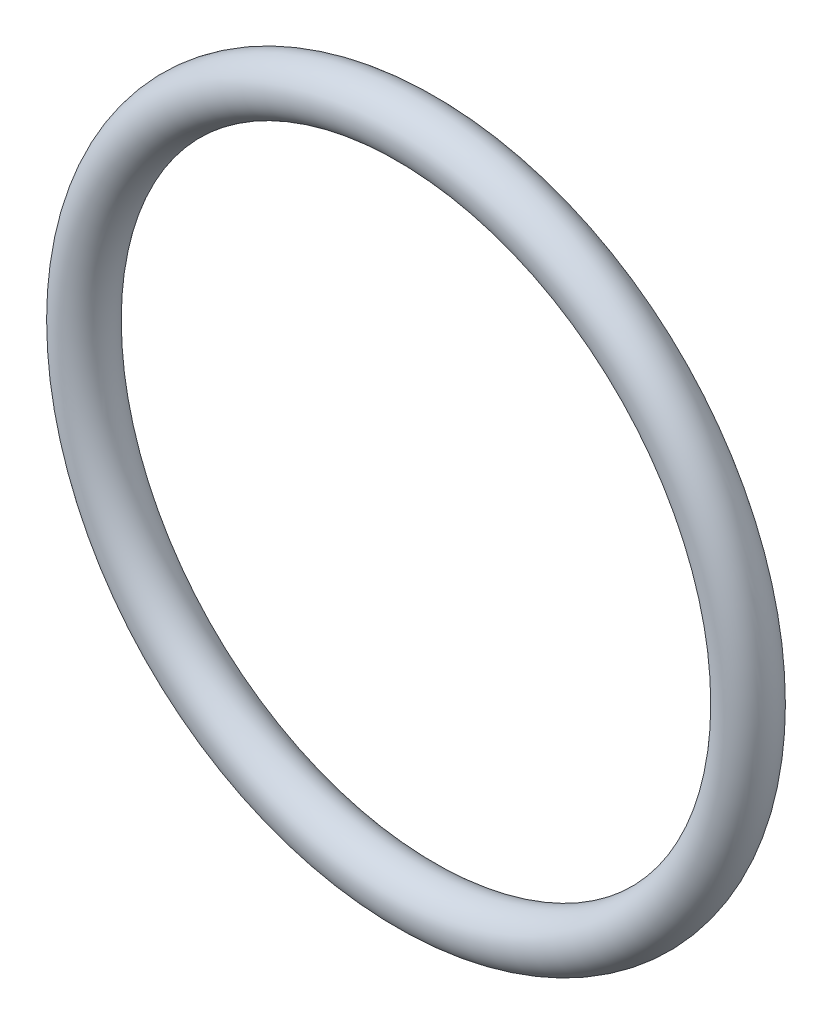
SolidWorks part; units mm, degrees
ref_plane "Front Plane" through (0, 0, 0) normal (0, 0, 1) x (1, 0, 0)
ref_plane "Top Plane" through (0, 0, 0) normal (0, 1, 0) x (1, 0, 0)
ref_plane "Right Plane" through (0, 0, 0) normal (1, 0, 0) x (0, 0, -1)
sketch "Sketch1" plane through (0, 0, 0) normal (0, 0, 1) x (1, 0, 0)
  line L0 (-23.9649, 0) -> (23.9649, 0) construction
  line L1 (-20.4343, 0) -> (20.4343, 0) construction
  line L2 (-16.9457, 16.9457) -> (16.9457, -16.9457) construction
  point P3 (20.4343, 0)
  point P4 (0, 0)
  point P8 (0, 0)
  point P9 (0, 0)
  point P10 (-23.9649, 0)
  point P11 (-20.4343, 0)
  point P14 (0, 0)
  point P15 (16.9457, -16.9457)
  point P16 (23.9649, 0)
  dimension "Actual OD" = 47.9298
  dimension "Actual ID" = 40.8686
  dimension "Actual Width" = 3.5306
  dimension "D1" = 45
sketch "Sketch2" plane through (0, 0, 0) normal (0, 1, 0) x (1, 0, 0)
  line L0 (-23.9649, 0) -> (23.9649, 0) construction
  line L1 (-22.1996, 1.7653) -> (-22.1996, -1.7653) construction
  line L2 (0, -1.7653) -> (0, 1.7653) construction
  circle A0 centre (-22.1996, 0) radius 1.7653
  point P12 (0, 0)
revolve "Revolve1" add sketch "Sketch2" angle 360 about L2
sketch "Sketch3" plane through (0, 0, 0) normal (1, 0, 0) x (0, 0, -1)
  line L0 (-1.7653, 0) -> (1.7653, 0) construction
  line L1 (-1.7653, -15.3257) -> (-1.7653, 15.3257) construction
  point P4 (0, 0)
  point P7 (-1.7653, 0)
  point P9 (-1.7653, -15.3257)
  dimension "D1" = 3.5306
  dimension "D2" = 30.6515
ref_axis "Axis1" through (0, 0, -1.9418) along (0, 0, 1)
equation "\"D1@Sketch3\"=\"Actual Width@Sketch1\""
equation "\"D2@Sketch3\"=\"Actual ID@Sketch1\"*.75"
